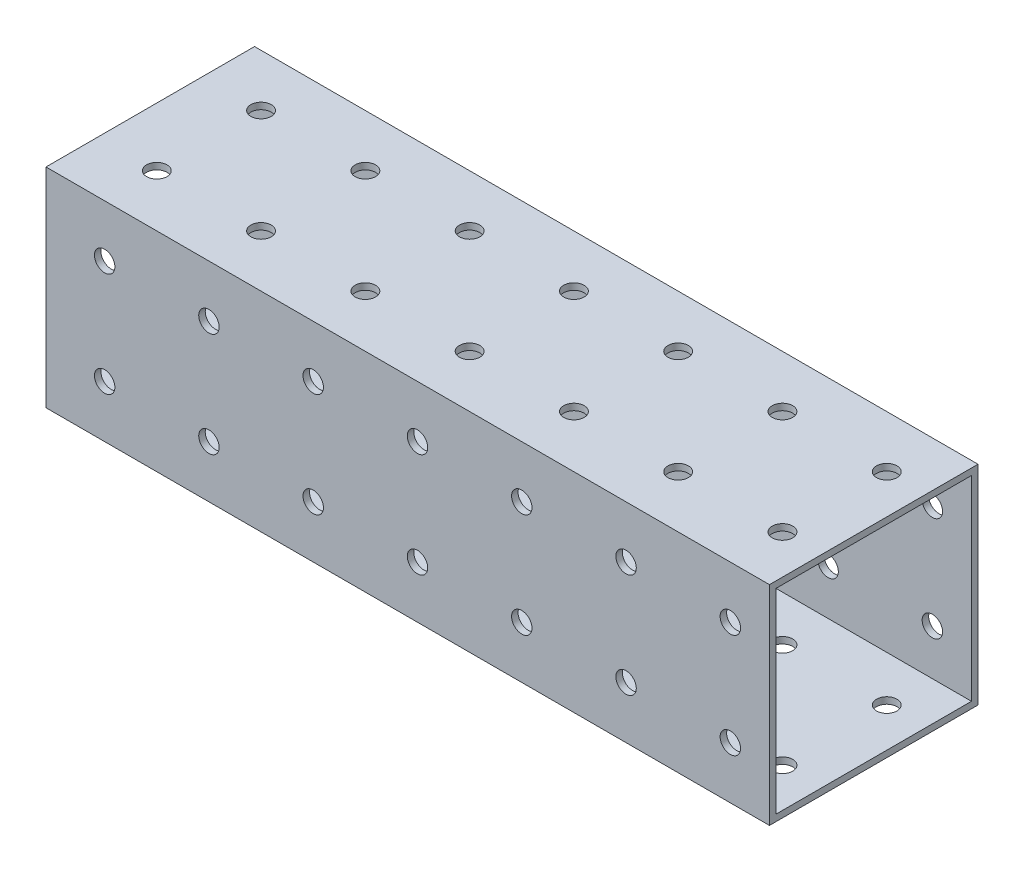
SolidWorks part; units mm, degrees
material "6061-T6 (SS)"
ref_plane "Front Plane" through (0, 0, 0) normal (0, 0, 1) x (1, 0, 0)
ref_plane "Top Plane" through (0, 0, 0) normal (0, 1, 0) x (1, 0, 0)
ref_plane "Right Plane" through (0, 0, 0) normal (1, 0, 0) x (0, 0, -1)
sketch "Sketch1" plane through (0, 0, 0) normal (1, 0, 0) x (0, 0, -1)
  line L1 (0, 0) -> (50.8, 0)
  line L2 (0, 0) -> (0, 50.8)
  line L3 (0, 50.8) -> (50.8, 50.8)
  line L4 (50.8, 0) -> (50.8, 50.8)
  dimension "D1" = 50.8
extrude "Boss-Extrude1" add sketch "Sketch1" along normal blind 176.2125
shell "Shell1" thickness 1.5875 removed face at (0, 25.4, -25.4) removed face at (176.2125, 25.4, -25.4)
sketch "Sketch2" plane through (0, 0, -50.8) normal (0, 0, -1) x (-1, 0, 0)
  line L0 (-166.6875, 0) -> (-166.6875, 50.8) construction
  line L1 (-176.2125, 0) -> (0, 0) construction
  line L2 (-176.2125, 50.8) -> (0, 50.8) construction
  line L3 (-176.2125, 0) -> (-176.2125, 50.8) construction
  circle A22 centre (-166.6875, 38.1) radius 2.4892
  circle A23 centre (-166.6875, 12.7) radius 2.4892
  dimension "D2" = 4.9784
  dimension "D3" = 25.4
  dimension "D4" = 12.7
  dimension "D1" = 9.525
extrude "Cut-Extrude3" cut sketch "Sketch2" against normal through all
sketch "Sketch3" plane through (0, 0, 0) normal (0, -1, 0) x (1, 0, 0)
  line L0 (166.6875, 0) -> (166.6875, -50.8) construction
  line L1 (176.2125, 0) -> (0, 0) construction
  line L2 (176.2125, -50.8) -> (0, -50.8) construction
  line L5 (176.2125, -50.8) -> (176.2125, 0) construction
  circle A2 centre (166.6875, -12.7) radius 2.4892
  circle A3 centre (166.6875, -38.1) radius 2.4892
  dimension "D1" = 4.9784
  dimension "D2" = 12.7
  dimension "D3" = 25.4
  dimension "D4" = 9.525
extrude "Cut-Extrude2" cut sketch "Sketch3" against normal through all
pattern_linear "LPattern1" count 7 spacing 25.4 along (-1, 0, 0) of "Cut-Extrude2", "Cut-Extrude3"
